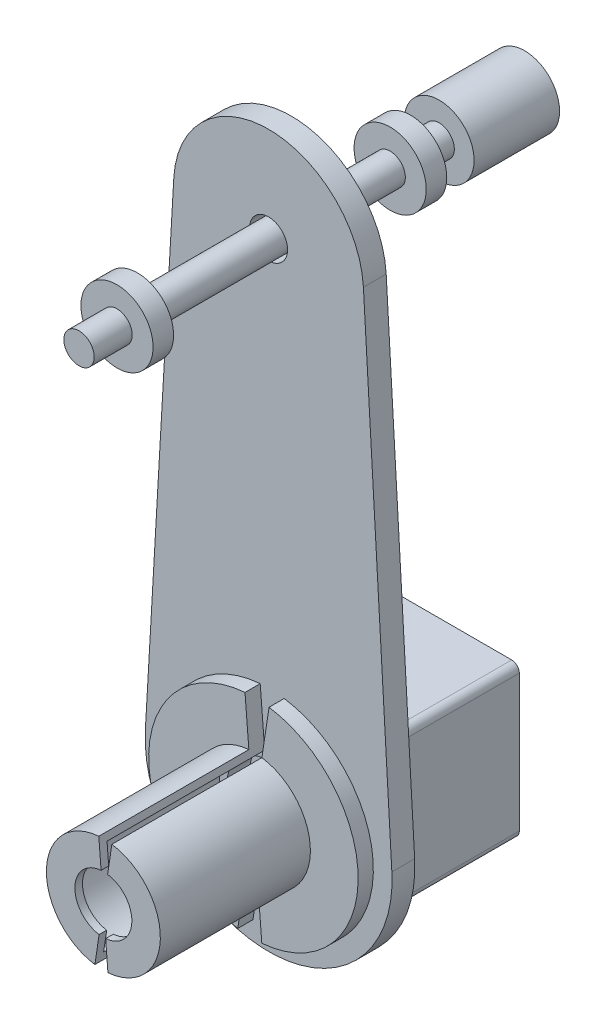
SolidWorks part; units mm, degrees
ref_plane "Front Plane" through (0, 0, 0) normal (0, 0, 1) x (1, 0, 0)
ref_plane "Top Plane" through (0, 0, 0) normal (0, 1, 0) x (1, 0, 0)
ref_plane "Right Plane" through (0, 0, 0) normal (1, 0, 0) x (0, 0, -1)
sketch "Sketch1" plane through (0, 0, 0) normal (0, 0, 1) x (1, 0, 0)
  line L0 (-24.9584, 131.4423) -> (-32.4459, 1.875)
  line L1 (24.9584, 131.4423) -> (32.4459, 1.875)
  line L2 (-20, 20) -> (20, -20)
  line L3 (-18, 20) -> (18, 20)
  line L4 (-20, 18) -> (-20, -18)
  line L5 (-18, -20) -> (18, -20)
  line L6 (20, 18) -> (20, -18)
  circle A0 centre (0, 0) radius 32.5
  circle A1 centre (0, 130) radius 25
  arc A2 (20, 18) -> (18, 20) centre (18, 18) ccw
  arc A3 (18, -20) -> (20, -18) centre (18, -18) ccw
  arc A4 (-18, -20) -> (-20, -18) centre (-18, -18) cw
  arc A5 (-18, 20) -> (-20, 18) centre (-18, 18) ccw
  circle A6 centre (0, 130) radius 5
  circle A7 centre (0, 0) radius 11
  circle A8 centre (0, 0) radius 2.5
  point P15 (20, 20)
  point P21 (-20, -20)
  dimension "D1" = 130
  dimension "D2" = 65
  dimension "D3" = 50
  dimension "D6" = 2
  dimension "D4" = 40
  dimension "D5" = 40
extrude "Boss-Extrude1" add sketch "Sketch1" along normal blind 6 contours A1 L0 A0 L1 | A1 A6 | A0 A5 L3 A2 L6 A3 L5 A4 L4 | A7 L2 A3 L6 A2 L3 A5 | A7 L2 A5 L4 A4 L5 A3 region at (0, 67.1478, 0) region at (0, 154.2929, 0) region at (0, 31.5808, 0) region at (-18.5521, 19.3328, 0) region at (-13.9903, 13.2021, 0)
extrude "Boss-Extrude2" add sketch "Sketch1<3>" against normal blind 40 contours A7 L2 A3 L6 A2 L3 A5 | A7 L2 A5 L4 A4 L5 A3 | L2 A7 | L2 A7 | L2 A8 | L2 A8 region at (-18.5521, 19.3328, 0) region at (-13.9903, 13.2021, 0) region at (3.4401, 3.4401, 0) region at (-3.4401, -3.4401, 0) region at (0.7503, 0.7503, 0) region at (-0.7503, -0.7503, 0)
sketch "Sketch1<3>" plane through (0, 0, 0) normal (0, 0, 1) x (1, 0, 0) same geometry as "Sketch1"
sketch "Sketch2" plane through (0, 0, 6) normal (0, 0, 1) x (1, 0, 0)
  line L0 (4.1133, 27.2685) -> (-4.1133, -27.2685)
  line L1 (-2.2109, 27.4882) -> (2.2109, -27.4882)
  circle A0 centre (0, 0) radius 27.577
  circle A1 centre (0, 0) radius 15
  circle A2 centre (0, 0) radius 7.5
  circle M5 centre (0, 0) radius 11
extrude "Boss-Extrude4" add sketch "Sketch2" along normal blind 4 contours A1 L1 A0 L0 | A1 L1 A0 L0 region at (20.4429, 17.5905, 6) region at (-2.3125, 21.1713, 6)
extrude "Boss-Extrude5" add sketch "Sketch2<3>" along normal blind 43.5 contours L1 A1 L0 M5 | L1 A1 L0 M5 | A2 L1 L0 M5 | A2 L1 L0 M5 region at (11.1203, 9.5687, 6) region at (8.1547, 7.0169, 6) region at (-1.3708, 12.9317, 6) region at (-0.9827, 9.2008, 6)
sketch "Sketch2<3>" plane through (0, 0, 6) normal (0, 0, 1) x (1, 0, 0) same geometry as "Sketch2"
sketch "Sketch3" plane through (0, 0, 0) normal (0, 0, -1) x (-1, 0, 0)
  circle A0 centre (0, 130) radius 4
extrude "Boss-Extrude6" add sketch "Sketch3" against normal blind 40.511 separate body
sketch "Sketch4" plane through (0, 0, 40.511) normal (0, 0, 1) x (1, 0, 0)
  circle A0 centre (0, 130) radius 9.5
  dimension "D1" = 19
extrude "Boss-Extrude7" add sketch "Sketch4" along normal blind 5.4
sketch "Sketch5" plane through (0, 0, 45.911) normal (0, 0, 1) x (1, 0, 0)
  circle A0 centre (0, 130) radius 4 construction
  circle A1 centre (0, 130) radius 4
extrude "Boss-Extrude8" add sketch "Sketch5" along normal blind 10
extrude "Boss-Extrude9" add sketch "Sketch3<2>" along normal blind 26
sketch "Sketch3<2>" plane through (0, 0, 0) normal (0, 0, -1) x (-1, 0, 0) same geometry as "Sketch3"
sketch "Sketch6" plane through (0, 0, -26) normal (0, 0, -1) x (-1, 0, 0)
  circle A0 centre (0, 130) radius 9.5 construction
  circle A1 centre (0, 130) radius 9.5
extrude "Boss-Extrude10" add sketch "Sketch6" along normal blind 5.4
sketch "Sketch7" plane through (0, 0, -31.4) normal (0, 0, -1) x (-1, 0, 0)
  circle A0 centre (0, 130) radius 4 construction
  circle A1 centre (0, 130) radius 9.5
  circle A2 centre (0, 130) radius 9.5
  circle A3 centre (0, 130) radius 4
  dimension "D1" = 0
extrude "Boss-Extrude12" add sketch "Sketch7" along normal blind 7.5 contours A3
sketch "Sketch8" plane through (0, 0, -38.9) normal (0, 0, -1) x (-1, 0, 0)
  circle A0 centre (0, 130) radius 9.2
extrude "Boss-Extrude13" add sketch "Sketch8" along normal blind 22.5
ref_plane "Plane1" through (0, 0, 0) normal (-1, 0, 0) x (0, 0, 1)
sketch "Sketch9" plane through (0, 0, 0) normal (-1, 0, 0) x (0, 0, 1)
  line L0 (49.5, -7.4759) -> (6, -7.4759) construction
  line L5 (6, 27.2685) -> (6, 10.8769) construction
  line L6 (6, 10.8769) -> (6, 7.4161) construction
  line L7 (6, 7.4161) -> (49.5, 7.4161) construction
  line L8 (49.5, 7.4161) -> (49.5, 14.8322) construction
  line L9 (49.5, 14.8322) -> (10, 14.8322) construction
  line L10 (10, 14.8322) -> (10, 27.2685) construction
  line L11 (10, 27.2685) -> (6, 27.2685) construction
  line L12 (6, -10.9646) -> (6, -27.4882) construction
  line L13 (6, -27.4882) -> (10, -27.4882) construction
  line L14 (10, -27.4882) -> (10, -14.9517) construction
  line L15 (10, -14.9517) -> (49.5, -14.9517) construction
  line L16 (49.5, -14.9517) -> (49.5, -7.4759) construction
  line L17 (6, -7.4759) -> (6, -10.9646) construction
  line L18 (6, 27.2685) -> (6, 10.8769)
  line L19 (6, 10.8769) -> (6, 7.4161)
  line L20 (6, 7.4161) -> (49.5, 7.4161)
  line L21 (49.5, 7.4161) -> (49.5, 14.8322)
  line L22 (49.5, 14.8322) -> (10, 14.8322)
  line L23 (10, 14.8322) -> (10, 27.2685)
  line L24 (10, 27.2685) -> (6, 27.2685)
  line L25 (6, -10.9646) -> (6, -27.4882)
  line L26 (6, -27.4882) -> (10, -27.4882)
  line L27 (10, -27.4882) -> (10, -14.9517)
  line L28 (10, -14.9517) -> (49.5, -14.9517)
  line L29 (49.5, -14.9517) -> (49.5, -7.4759)
  line L30 (49.5, -7.4759) -> (6, -7.4759)
  line L31 (6, -7.4759) -> (6, -10.9646)
  line L32 (6, -12.9517) -> (47.5, -12.9517)
  line L33 (47.5, -12.9517) -> (47.5, -7.4759)
  line L34 (3.4248, 0) -> (52.5811, 0) construction
  dimension "D1" = 2
  dimension "D2" = 2
revolve "Cut-Revolve1" cut sketch "Sketch9" angle 360 about L34 region at (0, -10.2138, 26.75)
